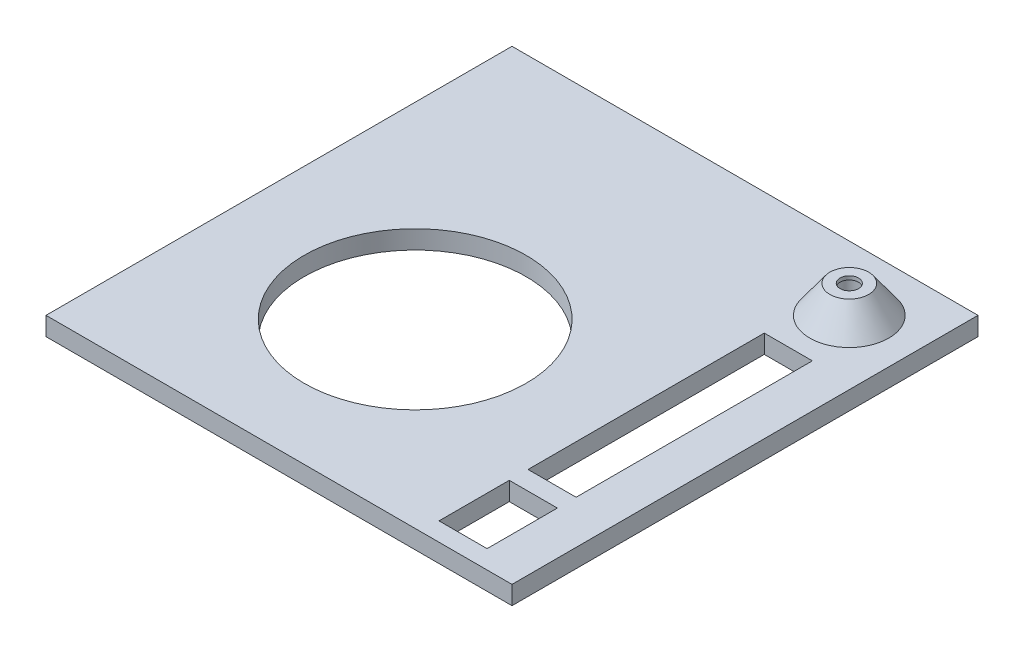
SolidWorks part; units mm, degrees
ref_plane "Front Plane" through (0, 0, 0) normal (0, 0, 1) x (1, 0, 0)
ref_plane "Top Plane" through (0, 0, 0) normal (0, 1, 0) x (1, 0, 0)
ref_plane "Right Plane" through (0, 0, 0) normal (1, 0, 0) x (0, 0, -1)
sketch "Sketch1" plane through (0, 0, 0) normal (0, 1, 0) x (1, 0, 0)
  line L1 (0, 0) -> (126, 0)
  line L2 (0, 0) -> (0, 126)
  line L3 (0, 126) -> (126, 126)
  line L4 (126, 0) -> (126, 126)
  dimension "D1" = 126
  dimension "D2" = 126
extrude "Boss-Extrude1" add sketch "Sketch1" along normal blind 5
sketch "Sketch3" plane through (0, 5, 0) normal (0, 1, 0) x (1, 0, 0)
  line L0 (108.6, 121.1) -> (108.6, 96.1) construction
  circle A0 centre (108.6, 108.6) radius 12.5
extrude "Boss-Extrude2" add sketch "Sketch3" along normal blind 7.5
sketch "Sketch4" plane through (0, 0, 0) normal (0, -1, 0) x (1, 0, 0)
  circle A1 centre (108.6, -108.6) radius 2.95
  dimension "D1" = 5.9
extrude "Cut-Extrude1" cut sketch "Sketch4" against normal blind 11.5
sketch "Sketch6" plane through (0, 12.5, 0) normal (0, 1, 0) x (1, 0, 0)
  line L0 (108.6, 121.1) -> (108.6, 96.1) construction
  circle A0 centre (108.6, 108.6) radius 12.5 construction
  circle A1 centre (108.6, 108.6) radius 2.5
  dimension "D1" = 5
extrude "Cut-Extrude2" cut sketch "Sketch6" against normal through all
chamfer "Chamfer1" distance 10 angle 36 1 edges at (108.6, 12.5, -96.1) first distance on face at (108.6, 12.5, -96.1)
sketch "Sketch8" plane through (0, 5, 0) normal (0, 1, 0) x (1, 0, 0)
  line L7 (114.2633, 24) -> (101.2633, 24)
  line L8 (114.2633, 24) -> (114.2633, 5)
  line L9 (114.2633, 5) -> (101.2633, 5)
  line L10 (101.2633, 24) -> (101.2633, 5)
  line L11 (114.2633, 24) -> (101.2633, 5) construction
  line L12 (114.2633, 5) -> (101.2633, 24) construction
  line L13 (114.2633, 24) -> (101.2633, 24)
  line L21 (114.2633, 29.0695) -> (101.2633, 29.0695)
  line L22 (114.2633, 29.0695) -> (114.2633, 92.9492)
  line L23 (114.2633, 92.9492) -> (101.2633, 92.9492)
  line L24 (101.2633, 29.0695) -> (101.2633, 92.9492)
  line L25 (114.2633, 29.0695) -> (101.2633, 92.9492) construction
  line L26 (114.2633, 92.9492) -> (101.2633, 29.0695) construction
  point P11 (107.7633, 14.5)
  point P17 (107.7633, 61.0093)
  dimension "D2" = 13
  dimension "D3" = 19
extrude "Cut-Extrude3" cut sketch "Sketch8" against normal through all contours L24 L21 L22 L23 | L7 L10 L9 L8 region at (107.7633, 5, -14.5) region at (107.7633, 5, -61.0093)
sketch "Sketch9" plane through (0, 5, 0) normal (0, 1, 0) x (1, 0, 0)
  circle A0 centre (50.8372, 48.9746) radius 30
  dimension "D1" = 60
extrude "Cut-Extrude4" cut sketch "Sketch9" against normal through all
sketch "Sketch10" plane through (0, 5, 0) normal (0, 1, 0) x (1, 0, 0)
  line L0 (50.8372, 78.9746) -> (50.8372, 18.9746) construction
  line L2 (18.1023, 67.874) -> (18.1023, 30.0751)
  line L3 (18.1023, 30.0751) -> (50.8372, 11.1757)
  line L4 (50.8372, 11.1757) -> (83.572, 30.0751)
  line L5 (83.572, 30.0751) -> (83.572, 67.874)
  line L6 (83.572, 67.874) -> (50.8372, 86.7735)
  line L7 (50.8372, 86.7735) -> (18.1023, 67.874)
  circle A0 centre (50.8372, 48.9746) radius 30 construction
  circle A1 centre (50.8372, 48.9746) radius 32.7348 construction
